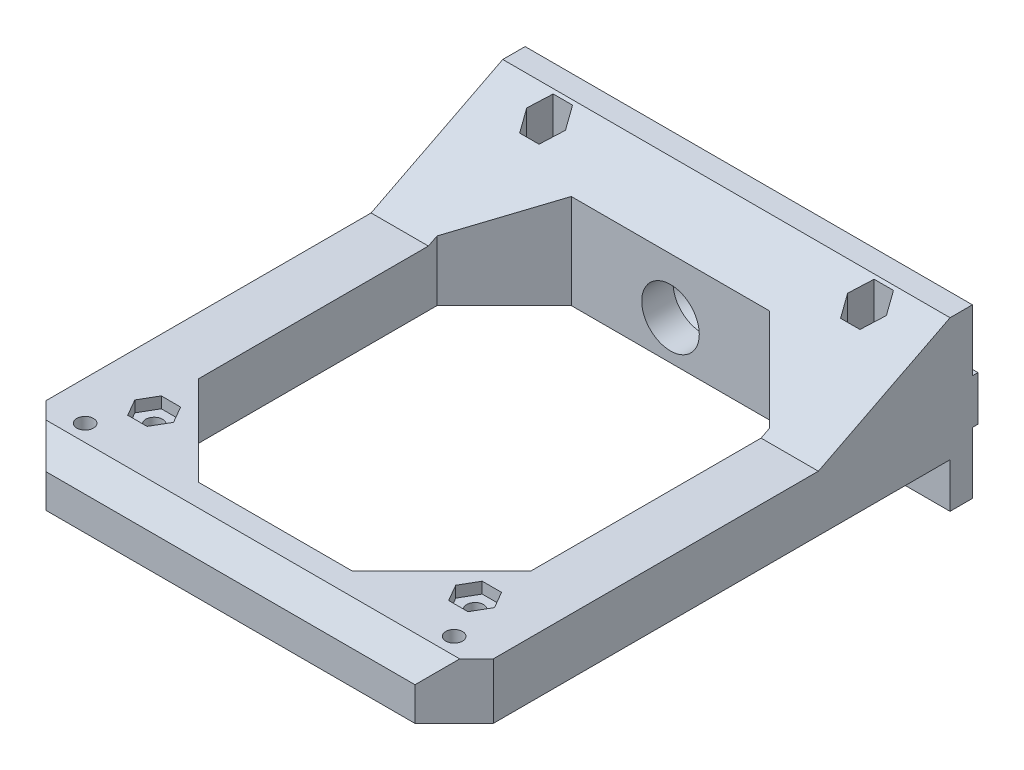
SolidWorks part; units mm, degrees
ref_plane "Top Plane" through (0, 0, 0) normal (0, 0, 1) x (1, 0, 0)
ref_plane "Right Plane" through (0, 0, 0) normal (0, 1, 0) x (1, 0, 0)
ref_plane "Front Plane" through (0, 0, 0) normal (1, 0, 0) x (0, 0, -1)
sketch "Sketch1" plane through (0, 0, 0) normal (1, 0, 0) x (0, 0, -1)
  line L0 (0, 4) -> (0, 15)
  line L1 (1, 4) -> (0, 4)
  line L2 (1, 4) -> (1, -4)
  line L3 (1, -4) -> (0, -4)
  line L5 (0, -15) -> (-4, -15)
  line L6 (0, -15) -> (0, -4)
  line L7 (0, 15) -> (-4, 15)
  line L8 (-4, -15) -> (-4, 15)
  line L9 (0, -4) -> (0, 4) construction
  point P9 (-5.0103, -15)
  dimension "D1" = 8
  dimension "D2" = 1
  dimension "D3" = 30
  dimension "D4" = 4
extrude "Boss-Extrude1" add sketch "Sketch1" along normal mid plane 80
sketch "Sketch2" plane through (-40, 0, 0) normal (-1, 0, 0) x (0, 0, 1)
  line L0 (4, 15) -> (4, -15) construction
  line L1 (4, 3) -> (14, 3)
  line L2 (4, 3) -> (4, -7)
  line L3 (4, -7) -> (14, -7)
  line L4 (14, 3) -> (14, -7)
  line L5 (0, 15) -> (4, 15) construction
  dimension "D1" = 22
  dimension "D2" = 10
  dimension "D3" = 10
extrude "Boss-Extrude2" add sketch "Sketch2" against normal up to surface (80 mm away) up to face at (40, 0, 0.75)
sketch "Sketch3" plane through (0, -7, 0) normal (0, -1, 0) x (1, 0, 0)
  line L0 (0, 4) -> (0, 4.5) construction
  line L1 (-31.75, 4.5) -> (31.75, 4.5) construction
  line L2 (-31.75, 4.5) -> (-31.75, 80.7) construction
  line L3 (-31.75, 80.7) -> (31.75, 80.7) construction
  line L4 (31.75, 4.5) -> (31.75, 80.7) construction
  line L5 (40, 4) -> (-40, 4) construction
  line L6 (40, 4) -> (-40, 4) construction
  line L7 (-31.75, 80.7) -> (31.75, 4.5) construction
  line L9 (-28.7, 7.55) -> (28.7, 7.55) construction
  line L10 (-28.7, 7.55) -> (-28.7, 77.65) construction
  line L11 (-28.7, 77.65) -> (28.7, 77.65) construction
  line L12 (28.7, 7.55) -> (28.7, 77.65) construction
  line L13 (-28.7, 7.55) -> (28.7, 77.65) construction
  line L14 (-28.7, 77.65) -> (28.7, 7.55) construction
  circle A0 centre (-28.7, 7.55) radius 1.5
  circle A1 centre (28.7, 7.55) radius 1.5
  point P10 (0, 42.6)
  dimension "D6" = 3
  dimension "D1" = 76.2
  dimension "D2" = 63.5
  dimension "D3" = 0.5
  dimension "D4" = 70.1
  dimension "D5" = 57.4
extrude "Cut-Extrude1" cut sketch "Sketch3" against normal through all
sketch "Sketch4" plane through (0, -7, 0) normal (0, -1, 0) x (1, 0, 0)
  line L1 (-40, 14) -> (-29.75, 14)
  line L2 (-40, 14) -> (-40, 92.7)
  line L3 (-40, 92.7) -> (40, 92.7)
  line L4 (-29.75, 14) -> (-29.75, 72.7)
  line L5 (-31.75, 4.5) -> (-31.75, 80.7) construction
  line L6 (-31.75, 80.7) -> (31.75, 80.7) construction
  line L9 (-29.75, 72.7) -> (-25.75, 72.7)
  line L10 (-25.75, 84.7) -> (-25.75, 72.7)
  line L11 (0, 42.6) -> (0, 14) construction
  line L12 (40, 14) -> (-40, 14) construction
  line L13 (40, 14) -> (40, 92.7)
  line L14 (40, 14) -> (29.75, 14)
  line L15 (29.75, 14) -> (29.75, 72.7)
  line L16 (29.75, 72.7) -> (25.75, 72.7)
  line L17 (25.75, 84.7) -> (25.75, 72.7)
  line L20 (-25.75, 84.7) -> (25.75, 84.7)
  circle A0 centre (-28.7, 77.65) radius 1.5
  circle A1 centre (28.7, 77.65) radius 1.5
  point P11 (62.4766, 84.7)
  point P26 (0, 0)
  point P29 (79.0156, 92.5212)
  dimension "D2" = 3
  dimension "D1" = 2
  dimension "D3" = 8
  dimension "D4" = 8
  dimension "D5" = 6
  dimension "D6" = 4
extrude "Boss-Extrude3" add sketch "Sketch4" against normal up to surface (10 mm away) up to face at (-28.7, 3, 9.05)
chamfer "Chamfer1" distance 12 angle 63 1 edges at (0, 3, 4) first distance on face at (0, 9, 4)
chamfer "Chamfer2" distance 4 angle 45 2 edges at (-29.75, -2, 72.7) (29.75, -2, 72.7)
chamfer "Chamfer3" distance 4 angle 45 1 edges at (0, 3, 92.7)
chamfer "Chamfer4" distance 12 angle 45 4 edges at (-25.75, -2, 84.7) (25.75, -2, 84.7) (29.75, 1.4524, 14) (-29.75, 1.4524, 14)
sketch "Sketch7" plane through (0, -7, 0) normal (0, -1, 0) x (1, 0, 0)
  line L0 (-40, 92.7) -> (-33, 85.7) construction
  line L1 (-33, 85.7) -> (-33, 92.7) construction
  line L2 (40, 92.7) -> (-40, 92.7) construction
  line L3 (-33, 85.7) -> (33, 85.7) construction
  line L4 (-40, 4) -> (-40, 92.7) construction
  line L5 (-40, 85.7) -> (-33, 85.7) construction
  line L6 (33, 85.7) -> (0, 92.7) construction
  line L7 (0, 92.7) -> (0, 85.7) construction
  circle A0 centre (-33, 85.7) radius 1.5
  circle A1 centre (33, 85.7) radius 1.5
  point P5 (0, 0)
  dimension "D1" = 3
  dimension "D2" = 7
extrude "Cut-Extrude3" cut sketch "Sketch7" against normal through all
sketch "Sketch5" plane through (0, 3, 0) normal (0, 1, 0) x (1, 0, 0)
  line L0 (32.1641, -77.65) -> (30.4321, -80.65)
  line L1 (30.4321, -80.65) -> (26.9679, -80.65)
  line L2 (26.9679, -80.65) -> (25.2359, -77.65)
  line L3 (25.2359, -77.65) -> (26.9679, -74.65)
  line L4 (26.9679, -74.65) -> (30.4321, -74.65)
  line L5 (30.4321, -74.65) -> (32.1641, -77.65)
  line L6 (-28.7, -77.65) -> (-28.7, -7.55) construction
  line L8 (0, -42.6) -> (0, -77.65) construction
  line L9 (0, -77.65) -> (-28.7, -77.65) construction
  line L10 (-28.7, -42.6) -> (28.7, -42.6) construction
  line L11 (-26.9679, -74.65) -> (-30.4321, -74.65)
  line L12 (-25.2359, -77.65) -> (-26.9679, -74.65)
  line L13 (28.7, -77.65) -> (28.7, -7.55) construction
  line L14 (-26.9679, -80.65) -> (-25.2359, -77.65)
  line L15 (-30.4321, -80.65) -> (-26.9679, -80.65)
  line L16 (-32.1641, -77.65) -> (-30.4321, -80.65)
  line L17 (-30.4321, -74.65) -> (-32.1641, -77.65)
  line L18 (-25.2359, -7.55) -> (-26.9679, -10.55)
  line L19 (-26.9679, -4.55) -> (-25.2359, -7.55)
  line L20 (-30.4321, -4.55) -> (-26.9679, -4.55)
  line L21 (-32.1641, -7.55) -> (-30.4321, -4.55)
  line L22 (-30.4321, -10.55) -> (-32.1641, -7.55)
  line L23 (-26.9679, -10.55) -> (-30.4321, -10.55)
  line L24 (26.9679, -10.55) -> (30.4321, -10.55)
  line L25 (25.2359, -7.55) -> (26.9679, -10.55)
  line L26 (26.9679, -4.55) -> (25.2359, -7.55)
  line L27 (30.4321, -4.55) -> (26.9679, -4.55)
  line L28 (32.1641, -7.55) -> (30.4321, -4.55)
  line L29 (30.4321, -10.55) -> (32.1641, -7.55)
  circle A0 centre (28.7, -77.65) radius 3.4641 construction
  dimension "D1" = 6
extrude "Cut-Extrude2" cut sketch "Sketch5" against normal blind 2 and the other way through all
chamfer "Chamfer5" distance 7 angle 45 2 edges at (-40, -4, 92.7) (40, -4, 92.7)
sketch "Sketch8" plane through (0, 0, 14) normal (0, 0, 1) x (1, 0, 0)
  circle A0 centre (0, 0) radius 5.15
  dimension "D1" = 10.3
extrude "Cut-Extrude4" cut sketch "Sketch8" against normal offset from surface (5.5 mm away) 8.5 up to face at (0, -9.5, 0)
sketch "Sketch9" plane through (0, 0, 8.5) normal (0, 0, 1) x (1, 0, 0)
  circle A0 centre (0, 0) radius 2.75
  dimension "D1" = 5.5
extrude "Cut-Extrude5" cut sketch "Sketch9" against normal through all
chamfer "Chamfer6" distance 2.5 angle 45 1 edges at (2.75, 0, 8.5)
